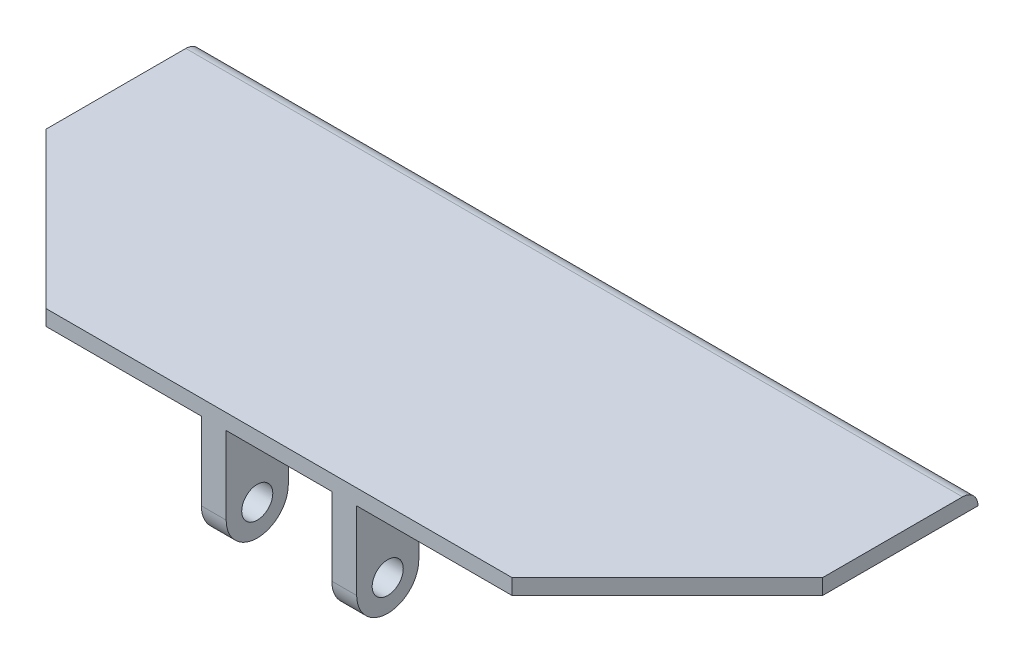
SolidWorks part; units mm, degrees
ref_plane "Front Plane" through (0, 0, 0) normal (0, 0, 1) x (1, 0, 0)
ref_plane "Top Plane" through (0, 0, 0) normal (0, 1, 0) x (1, 0, 0)
ref_plane "Right Plane" through (0, 0, 0) normal (1, 0, 0) x (0, 0, -1)
sketch "Sketch1" plane through (0, 0, 0) normal (0, 1, 0) x (1, 0, 0)
  line L1 (0, 0) -> (-250, 0)
  line L2 (0, 0) -> (0, 100)
  line L3 (0, 100) -> (-250, 100)
  line L4 (-250, 0) -> (-250, 100)
  dimension "D1" = 250
  dimension "D2" = 100
extrude "Boss-Extrude1" add sketch "Sketch1" along normal blind 5
chamfer "Chamfer2" distance 50 angle 45 2 edges at (-250, 2.5, 0) (0, 2.5, 0)
fillet "Fillet1" radius 5 1 edges at (-125, 5, -100)
sketch "Sketch2" plane through (0, 0, 0) normal (0, -1, 0) x (1, 0, 0)
  line L0 (-200, 0) -> (-50, 0) construction
  line L1 (-150, 0) -> (-142, 0)
  line L2 (-150, 0) -> (-150, -20)
  line L3 (-150, -20) -> (-142, -20)
  line L4 (-142, 0) -> (-142, -20)
  line L5 (-250, -100) -> (-250, -50) construction
  line L6 (0, -50) -> (0, -100) construction
  line L9 (-108, 0) -> (-100, 0)
  line L10 (-108, 0) -> (-108, -20)
  line L11 (-108, -20) -> (-100, -20)
  line L12 (-100, 0) -> (-100, -20)
  dimension "D1" = 20
  dimension "D2" = 8
  dimension "D3" = 100
  dimension "D4" = 100
extrude "Boss-Extrude2" add sketch "Sketch2" along normal blind 35
sketch "Sketch4" plane through (-100, 0, 0) normal (1, 0, 0) x (0, 0, -1)
  line L0 (20, -35) -> (0, -35) construction
  line L1 (0, -35) -> (0, 0) construction
  circle A0 centre (10, -25) radius 5
  dimension "D1" = 10
  dimension "D2" = 10
  dimension "D3" = 10
extrude "Cut-Extrude1" cut sketch "Sketch4" against normal through all
fillet "Fillet2" radius 10 4 edges at (-104, -35, -20) (-146, -35, -20) (-146, -35, 0) (-104, -35, 0)
